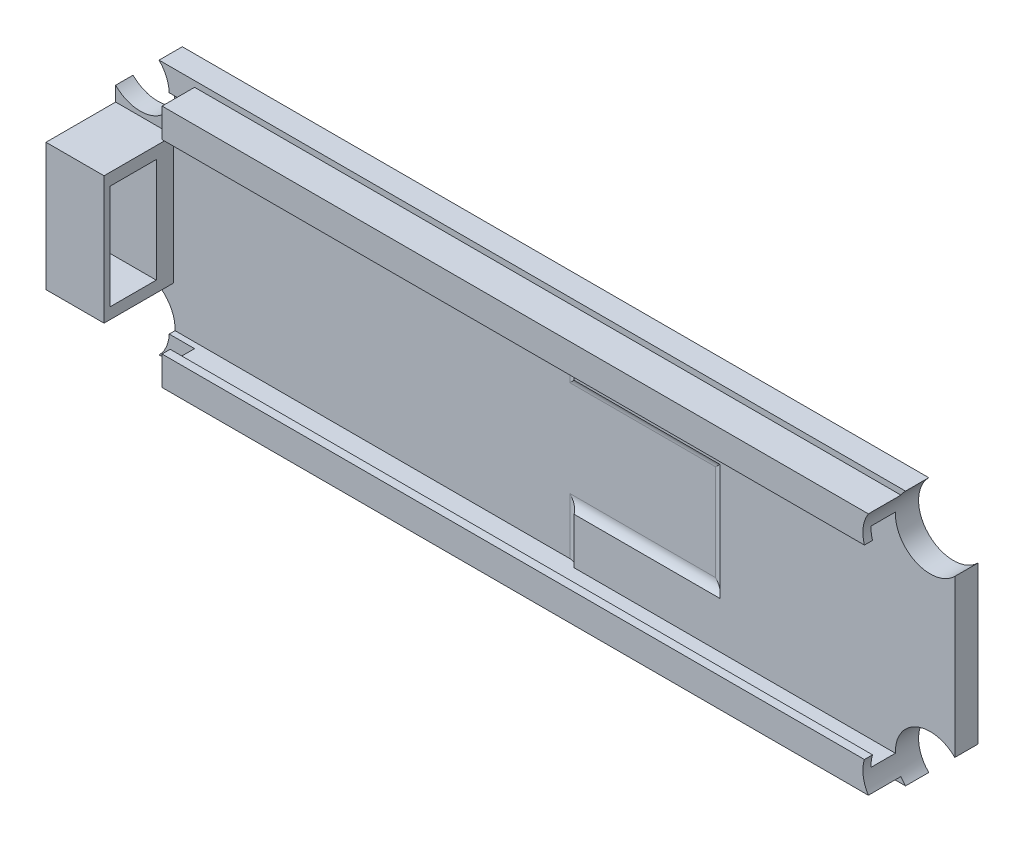
SolidWorks part; units mm, degrees
ref_plane "Ebene vorne" through (0, 0, 0) normal (1, 0, 0) x (0, 1, 0)
ref_plane "Ebene oben" through (0, 0, 0) normal (0, 0, 1) x (0, 1, 0)
ref_plane "Ebene rechts" through (0, 0, 0) normal (0, 1, 0) x (-1, 0, 0)
sketch "Skizze1" plane through (0, 0, 0) normal (0, 0, 1) x (0, 1, 0)
  line L30 (-11, -36.4) -> (11, -36.4)
  line L31 (-11, -36.4) -> (-11, 36.4)
  line L32 (-11, 36.4) -> (11, 36.4)
  line L33 (11, -36.4) -> (11, 36.4)
  line L34 (-11, -36.4) -> (11, 36.4) construction
  line L35 (-11, 36.4) -> (11, -36.4) construction
  point P0 (0, 0)
  dimension "D1" = 22
  dimension "D2" = 72.8
extrude "Aufsatz-Linear austragen1" add sketch "Skizze1" along normal blind 2
sketch "Skizze2" plane through (0, 0, 2) normal (0, 0, 1) x (1, 0, 0)
  line L0 (36.4, 11) -> (-36.4, 11) construction
  circle A0 centre (-34.28, 8.88) radius 3
  circle A1 centre (-34.28, -8.88) radius 3
  circle A2 centre (34.28, -8.88) radius 3
  circle A3 centre (34.28, 8.88) radius 3
  dimension "D3" = 6
  dimension "D6" = 6
  dimension "D9" = 6
  dimension "D12" = 6
  dimension "D1" = 2.12
  dimension "D2" = 2.12
  dimension "D4" = 2.12
  dimension "D5" = 2.12
  dimension "D7" = 2.12
  dimension "D8" = 2.12
  dimension "D10" = 2.12
  dimension "D11" = 2.12
extrude "Schnitt-Linear austragen1" cut sketch "Skizze2" against normal blind 2
sketch "Skizze3" plane through (0, 0, 2) normal (0, 0, 1) x (1, 0, 0)
  line L0 (-36.4, 0) -> (36.4, 0) construction
  line L1 (36.4, -10.5) -> (-29.1, -10.5)
  line L2 (36.4, -10.5) -> (36.4, 10.5)
  line L3 (36.4, 10.5) -> (-29.1, 10.5)
  line L4 (-29.1, -10.5) -> (-29.1, 10.5)
  line L5 (-36.4, 6.7574) -> (-36.4, -6.7574) construction
  line L6 (36.4, -6.7574) -> (36.4, 6.7574) construction
  dimension "D1" = 65.5
  dimension "D2" = 21
extrude "Aufsatz-Linear austragen2" add sketch "Skizze3" along normal blind 2.8
sketch "Skizze4" plane through (-29.1, 0, 0) normal (-1, 0, 0) x (0, -1, 0)
  line L0 (0, 0) -> (0, 2) construction
  line L1 (-8, 4.8) -> (8, 4.8)
  line L2 (-6.7574, 2) -> (6.7574, 2) construction
  line L3 (0, 2) -> (0, 4.8) construction
  line L4 (-10.5, 4.8) -> (10.5, 4.8) construction
  line L15 (-9, 2) -> (9, 2)
  line L16 (-9, 2) -> (-9, 4.1)
  line L17 (-9, 4.1) -> (9, 4.1) construction
  line L18 (9, 2) -> (9, 4.1)
  line L19 (-9, 2) -> (9, 4.1) construction
  line L20 (-9, 4.1) -> (9, 2) construction
  line L21 (-10.5, 4.8) -> (10.5, 4.8) construction
  line L22 (-9, 4.1) -> (-8, 4.1)
  line L23 (-8, 4.1) -> (-8, 4.8)
  line L24 (8, 4.8) -> (8, 4.1)
  line L25 (8, 4.1) -> (9, 4.1)
  point P2 (0, 3.4)
  point P5 (0, 3.05)
  point P6 (0, 3.4)
  point P20 (0, 4.8)
  dimension "D1" = 18
  dimension "D2" = 2.1
  dimension "D3" = 16
extrude "Schnitt-Linear austragen2" cut sketch "Skizze4" against normal through all
sketch "Skizze5" plane through (0, 0, 2) normal (0, 0, -1) x (1, 0, 0)
  line L0 (36.4, -11) -> (36.4, 11) construction
  line L2 (36.4, 6.7574) -> (36.4, -6.7574) construction
  circle A1 centre (34.28, -8.88) radius 3
  circle A2 centre (34.28, 8.88) radius 3
  point P3 (36.4, 0)
  dimension "D4" = 6
  dimension "D7" = 6
  dimension "D1" = 22
  dimension "D2" = 2.12
  dimension "D3" = 2.12
  dimension "D5" = 2.12
  dimension "D6" = 2.12
extrude "Schnitt-Linear austragen4" cut sketch "Skizze5" against normal through all
sketch "Skizze6" plane through (-36.4, 0, 0) normal (-1, 0, 0) x (0, -1, 0)
  line L0 (-6.7574, 2) -> (6.7574, 2) construction
  line L1 (-9, 2.5) -> (9, 2.5)
  line L2 (-9, 2.5) -> (-9, 1.5)
  line L3 (-9, 1.5) -> (9, 1.5)
  line L4 (9, 2.5) -> (9, 1.5)
  line L5 (-9, 2.5) -> (9, 1.5) construction
  line L6 (-9, 1.5) -> (9, 2.5) construction
  point P0 (0, 2)
  dimension "D1" = 18
  dimension "D2" = 1
extrude "Schnitt-Linear austragen5" cut sketch "Skizze6" against normal blind 40
sketch "Skizze8" plane through (0, 0, 2) normal (0, 0, 1) x (1, 0, 0)
  line L0 (1.156, -8) -> (1.156, 8) construction
  line L1 (1.156, -5.0073) -> (16.156, -5.0073)
  line L2 (1.156, -5.0073) -> (1.156, 4.9927)
  line L3 (1.156, 4.9927) -> (16.156, 4.9927)
  line L4 (16.156, -5.0073) -> (16.156, 4.9927)
  line L5 (31.412, -8) -> (-29.1, -8) construction
  line L8 (31.412, 8) -> (-29.1, 8) construction
  dimension "D1" = 10
  dimension "D2" = 15
extrude "Schnitt-Linear austragen6" cut sketch "Skizze8" against normal blind 0.5
fillet "Verrundung3" radius 1 5 edges at (3.6, -7.0037, 1.5) (9.878, -5.0073, 1.5) (3.6, 6.9963, 1.5) (9.878, 4.9927, 1.5) (16.156, -0.0073, 1.5)
sketch "Skizze9" plane through (0, 0, 1.5) normal (0, 0, 1) x (1, 0, 0)
  line L0 (-36.4, 6.7574) -> (-36.4, -6.7574) construction
  line L5 (-31.4, 5.5) -> (-36.4, 5.5)
  line L6 (-31.4, 5.5) -> (-31.4, -5.5)
  line L7 (-31.4, -5.5) -> (-36.4, -5.5)
  line L8 (-36.4, 5.5) -> (-36.4, -5.5)
  line L9 (-31.4, 5.5) -> (-36.4, -5.5) construction
  line L10 (-31.4, -5.5) -> (-36.4, 5.5) construction
  line L11 (-36.4, -6.7574) -> (-36.4, 6.7574) construction
  point P0 (-33.9, 0)
  point P8 (-36.4, 0)
  dimension "D1" = 11
  dimension "D2" = 5
extrude "Aufsatz-Linear austragen3" add sketch "Skizze9" along normal blind 6
sketch "Skizze10" plane through (-36.4, 0, 0) normal (-1, 0, 0) x (0, -1, 0)
  line L1 (-4.4618, 3) -> (4.5382, 3)
  line L2 (-4.4618, 3) -> (-4.4618, 7)
  line L3 (-4.4618, 7) -> (4.5382, 7)
  line L4 (4.5382, 3) -> (4.5382, 7)
  line L5 (-4.4618, 3) -> (4.5382, 7) construction
  line L6 (-4.4618, 7) -> (4.5382, 3) construction
  point P0 (0.0382, 5)
  dimension "D1" = 4
  dimension "D2" = 9
  dimension "D3" = 3
extrude "Schnitt-Linear austragen7" cut sketch "Skizze10" against normal through all
